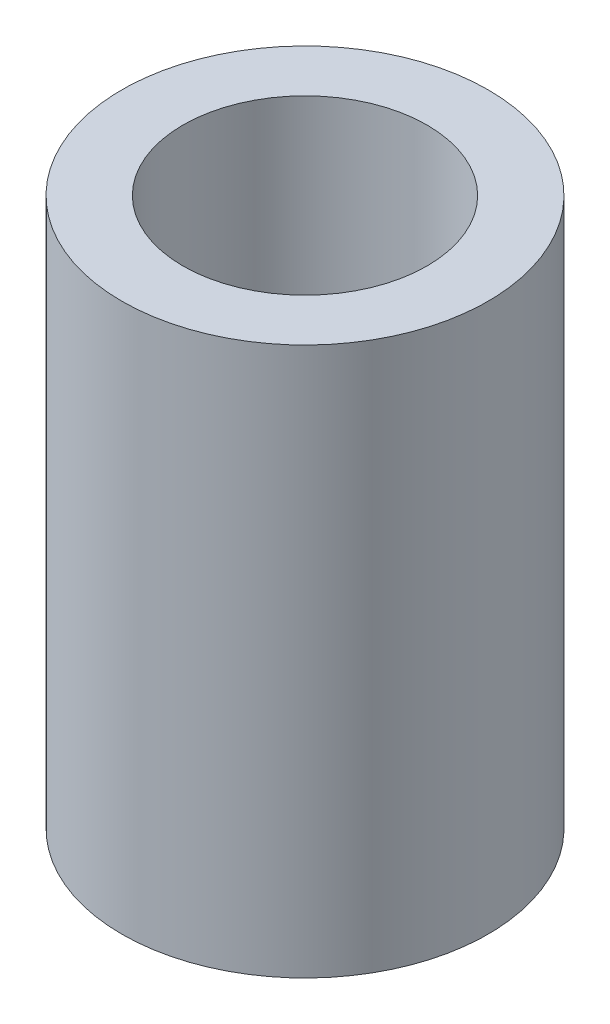
SolidWorks part; units mm, degrees
ref_plane "Front Plane" through (0, 0, 0) normal (0, 0, 1) x (1, 0, 0)
ref_plane "Top Plane" through (0, 0, 0) normal (0, 1, 0) x (1, 0, 0)
ref_plane "Right Plane" through (0, 0, 0) normal (1, 0, 0) x (0, 0, -1)
sketch "Sketch1" plane through (0, 0, 0) normal (0, 1, 0) x (1, 0, 0)
  circle A0 centre (0, 0) radius 2.54
  circle A1 centre (0, 0) radius 3.81
  dimension "D1" = 5.08
  dimension "D2" = 7.62
extrude "Boss-Extrude1" add sketch "Sketch1" along normal blind 11.4046
